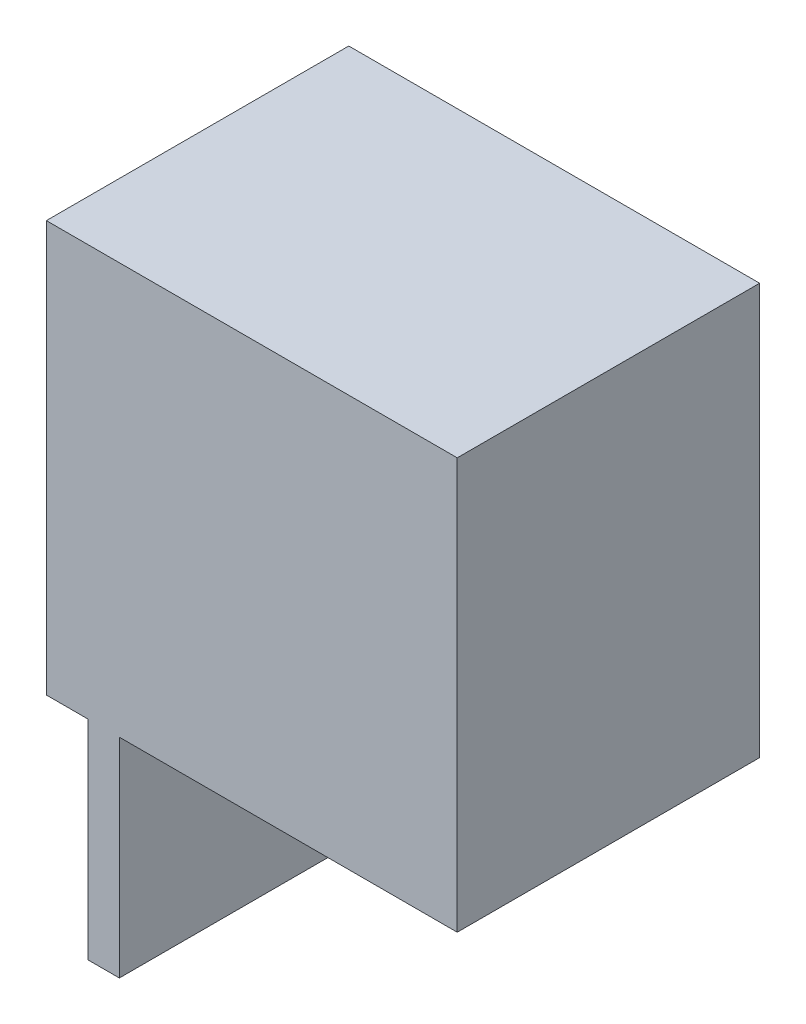
SolidWorks part; units mm, degrees
ref_plane "Front Plane" through (0, 0, 0) normal (0, 0, 1) x (1, 0, 0)
ref_plane "Top Plane" through (0, 0, 0) normal (0, 1, 0) x (1, 0, 0)
ref_plane "Right Plane" through (0, 0, 0) normal (1, 0, 0) x (0, 0, -1)
sketch "Sketch2" plane through (0, 0, 0) normal (0, 0, 1) x (1, 0, 0)
  line L1 (0, 0) -> (42.418, 0)
  line L2 (0, 0) -> (0, 42.418)
  line L3 (0, 42.418) -> (42.418, 42.418)
  line L4 (42.418, 0) -> (42.418, 42.418)
  line L5 (-3.81, 46.228) -> (46.228, 46.228)
  line L6 (-3.81, 46.228) -> (-3.81, -3.81)
  line L7 (-3.81, -3.81) -> (46.228, -3.81)
  line L8 (46.228, 46.228) -> (46.228, -3.81)
  dimension "D1" = 42.418
  dimension "D2" = 42.418
  dimension "D3" = 3.81
  dimension "D4" = 3.81
  dimension "D5" = 3.81
  dimension "D6" = 3.81
extrude "Boss-Extrude1" add sketch "Sketch2" along normal blind 34.29
sketch "Sketch4" plane through (0, 0, 34.29) normal (0, 0, 1) x (1, 0, 0)
  line L1 (-3.81, 46.228) -> (46.228, 46.228)
  line L2 (-3.81, 46.228) -> (-3.81, -3.81)
  line L3 (-3.81, -3.81) -> (46.228, -3.81)
  line L4 (46.228, 46.228) -> (46.228, -3.81)
extrude "Boss-Extrude2" add sketch "Sketch4" along normal blind 2.54
sketch "Sketch5" plane through (0, 0, 0) normal (0, 0, -1) x (-1, 0, 0)
  line L6 (3.81, -3.81) -> (-46.228, -3.81) construction
  line L7 (-5.08, -3.81) -> (-1.27, -3.81)
  line L8 (-5.08, -3.81) -> (-5.08, -29.21)
  line L9 (-5.08, -29.21) -> (-1.27, -29.21)
  line L10 (-1.27, -3.81) -> (-1.27, -29.21)
  line L11 (3.81, 46.228) -> (3.81, -3.81) construction
  dimension "D1" = 5.08
  dimension "D2" = 3.81
  dimension "D3" = 25.4
extrude "Boss-Extrude3" add sketch "Sketch5" against normal up to surface (36.83 mm away) up to face at (21.209, 21.209, 36.83)
